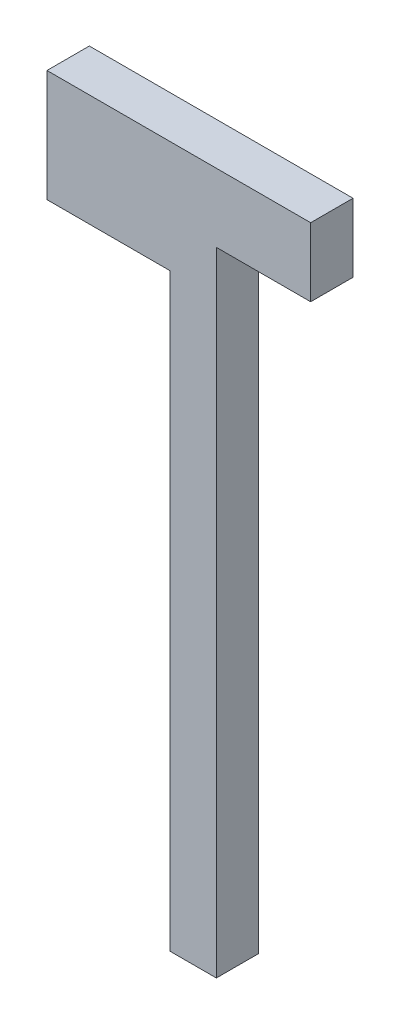
SolidWorks part; units mm, degrees
ref_plane "xy_plane" through (0, 0, 0) normal (0, 0, 1) x (1, 0, 0)
ref_plane "zx_plane" through (0, 0, 0) normal (0, 1, 0) x (1, 0, 0)
ref_plane "yz_plane" through (0, 0, 0) normal (1, 0, 0) x (0, 0, -1)
ref_plane "zMid_plane" through (0, 0, 0) normal (0, 0, 1) x (1, 0, 0)
ref_plane "zMin_plane" through (0, 0, -0.6173) normal (0, 0, 1) x (1, 0, 0)
ref_plane "zMax_plane" through (0, 0, 0.6173) normal (0, 0, 1) x (1, 0, 0)
ref_axis "x_axis" through (-80.9, 0, 0) along (1, 0, 0)
ref_axis "y_axis" through (0, -50, 0) along (0, 1, 0)
ref_axis "z_axis" through (0, 0, -80.9) along (0, 0, 1)
sketch "tSlotProfile_sketch" plane through (0, 0, 0) normal (0, 0, 1) x (1, 0, 0)
  line B0 (-28.5, -5.8) -> (-28.5, -5)
  line B1 (5.8, -30) -> (5.8, -28.5)
  line B2 (-5, -28.5) -> (-5.8, -28.5)
  line B3 (-5.8, -28.5) -> (-5.8, -30)
  line B4 (17.9899, -11.85) -> (11.85, -17.9899)
  line B5 (11.85, -17.9899) -> (11.85, -25.8)
  line B6 (11.85, -25.8) -> (7.5, -25.8)
  line B7 (7.5, -25.8) -> (7.5, -28.2)
  line B8 (7.5, -28.2) -> (25.7, -28.2)
  line B9 (28.2, -25.7) -> (28.2, -7.5)
  line B10 (25.8, -7.5) -> (25.8, -11.85)
  line B11 (25.8, -11.85) -> (17.9899, -11.85)
  line B12 (-11.85, -17.9899) -> (-17.9899, -11.85)
  line B13 (-17.9899, -11.85) -> (-25.8, -11.85)
  line B14 (-28.2, -7.5) -> (-28.2, -25.7)
  line B15 (-25.7, -28.2) -> (-7.5, -28.2)
  line B16 (-7.5, -28.2) -> (-7.5, -25.8)
  line B17 (-7.5, -25.8) -> (-11.85, -25.8)
  line B18 (-11.85, -25.8) -> (-11.85, -17.9899)
  line B19 (0.9, -15.2) -> (7.9956, -15.2)
  line B20 (7.9956, -15.2) -> (10.045, -17.2494)
  line B21 (0.9, -7.9995) -> (0.9, -15.2)
  line B22 (17.2494, 10.045) -> (10.045, 17.2494)
  line B23 (0.9, 15.2) -> (0.9, 7.9995)
  line B24 (-15.2, -0.9) -> (-15.2, -7.9956)
  line B25 (-17.2494, -10.045) -> (-10.045, -17.2494)
  line B26 (-10.045, -17.2494) -> (-7.9956, -15.2)
  line B27 (-7.9956, -15.2) -> (-0.9, -15.2)
  line B28 (-0.9, -15.2) -> (-0.9, -7.9995)
  line B29 (-28.5, -5) -> (-24, -5)
  line B30 (-24, -10.05) -> (-19.8, -10.05)
  line B31 (-24, 5) -> (-28.5, 5)
  line B32 (-27, 30) -> (-5.8, 30)
  line B33 (19.8, -10.05) -> (24, -10.05)
  line B34 (30, -5.8) -> (30, -27)
  line B35 (27, -30) -> (5.8, -30)
  line B36 (5, -28.5) -> (5, -24)
  line B37 (5, -24) -> (10.05, -24)
  line B38 (10.05, -24) -> (10.05, -19.8)
  line B39 (10.05, -19.8) -> (7.25, -17)
  line B40 (7.25, -17) -> (-7.25, -17)
  line B41 (-7.25, -17) -> (-10.05, -19.8)
  line B42 (-10.05, -19.8) -> (-10.05, -24)
  line B43 (-10.05, -24) -> (-5, -24)
  line B44 (-5, -24) -> (-5, -28.5)
  line B45 (-5.8, -30) -> (-27, -30)
  line B46 (-30, -27) -> (-30, -5.8)
  arc B47 (-0.9, 7.9995) -> (-7.9995, 0.9) centre (0, 0) ccw
sketch_block_instance "rexroth_60x60L-1"
sketch_block "Block1"
sketch "panelClipSection_sketch" plane through (0, 0, 0) normal (0, 0, 1) x (1, 0, 0)
  line L0 (-8.585, -24) -> (-5, -24)
  line L1 (-5, -24) -> (-5, -41.1744)
  line L2 (-5, -41.1744) -> (-3.6492, -41.1744)
  line L3 (-3.6492, -41.1744) -> (-3.6492, -22.735)
  line L4 (-3.6492, -22.735) -> (-0.9012, -22.735)
  line L5 (-0.9012, -22.735) -> (-0.9012, -20.7392)
  line L6 (-0.9012, -20.7392) -> (-8.585, -20.7392)
  line L7 (-8.585, -20.7392) -> (-8.585, -24)
  line L9 (0, -50) -> (0, 50) construction
  line L10 (-80.9, 0) -> (80.9, 0) construction
  dimension "d" = 3.2608
  dimension "c" = 2.748
  dimension "b" = 1.3508
  dimension "f" = 1.9958
  dimension "a" = 3.585
  dimension "e" = 17.1744
extrude "Boss-Extrude1" add sketch "panelClipSection_sketch" along normal up to surface (0.6173 mm away) from surface up to plane "zMax_plane" starting at plane "zMin_plane"
equation "\"D1@zMin_plane\"=\"externalParameters.this.extentZ\"/2"
equation "\"D1@zMax_plane\"=\"externalParameters.this.extentZ\"/2"
